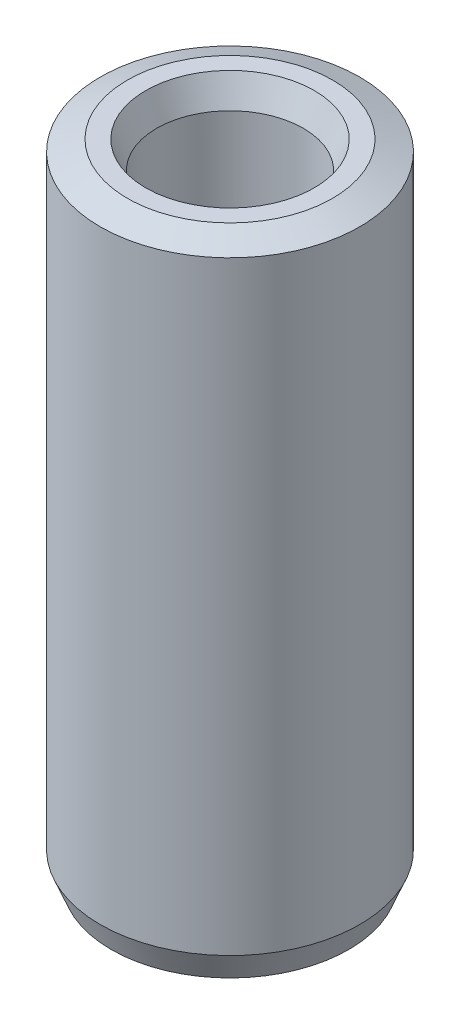
SolidWorks part; units mm, degrees
ref_plane "Front Plane" through (0, 0, 0) normal (0, 0, 1) x (1, 0, 0)
ref_plane "Top Plane" through (0, 0, 0) normal (0, 1, 0) x (1, 0, 0)
ref_plane "Right Plane" through (0, 0, 0) normal (1, 0, 0) x (0, 0, -1)
sketch "Sketch1" plane through (0, 0, 0) normal (0, 1, 0) x (1, 0, 0)
  circle A0 centre (0, 0) radius 42.5
  dimension "SLEEVE_OD" = 85
extrude "Boss-Extrude1" add sketch "Sketch1" along normal blind 210.4535
sketch "Sketch2" plane through (0, 0, 0) normal (0, 1, 0) x (1, 0, 0)
  circle A0 centre (0, 0) radius 24.0095
  dimension "BORE_D" = 48.019
extrude "Cut-Extrude1" cut sketch "Sketch2" along normal through all
chamfer "Chamfer1" distance 3.604 angle 67.965 4 edges at (0, 210.4535, 24.0095) (0, 0, 24.0095) (0, 0, 42.5) (0, 210.4535, 42.5) first distance on face at (0, 210.4535, 24.0095) first distance on face at (0, 0, 24.0095) first distance on face at (0, 210.4535, 42.5)
